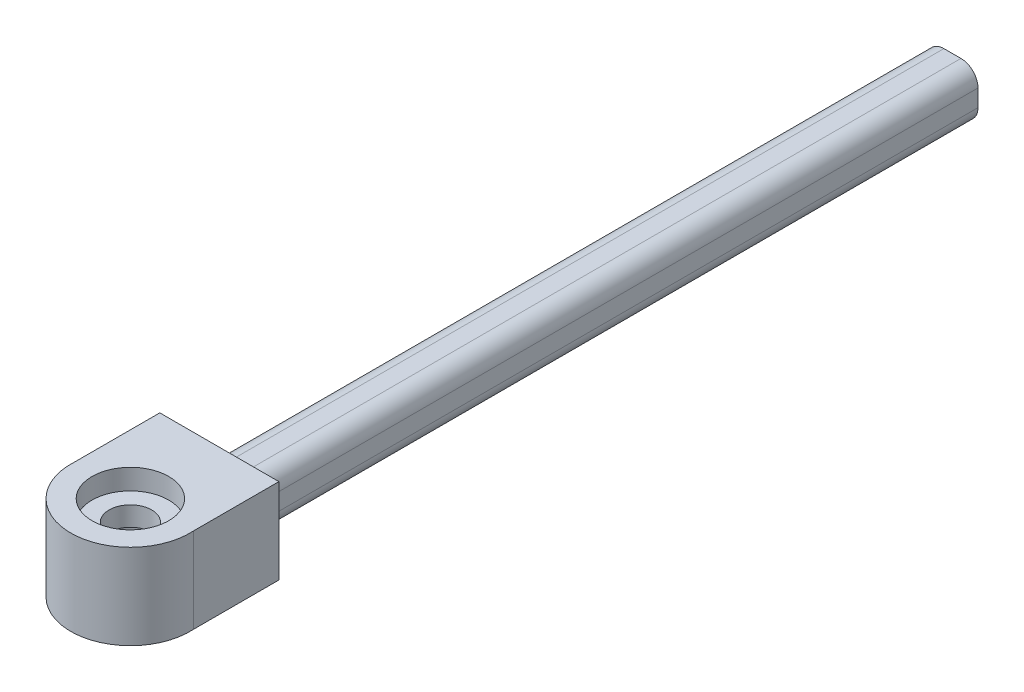
SolidWorks part; units mm, degrees
ref_plane "前视基准面" through (0, 0, 0) normal (0, 0, 1) x (1, 0, 0)
ref_plane "上视基准面" through (0, 0, 0) normal (0, 1, 0) x (1, 0, 0)
ref_plane "右视基准面" through (0, 0, 0) normal (1, 0, 0) x (0, 0, -1)
other "Configuration Table"
sketch "草图1" plane through (0, 0, 0) normal (0, 0, 1) x (1, 0, 0)
  line L0 (0, 0) -> (0, 48.7698) construction
  line L1 (-2.4, 0) -> (-3.5, 0)
  line L2 (-3.5, 0) -> (-3.5, 5)
  line L3 (-3.5, 5) -> (-2.25, 5)
  line L4 (-2.25, 5) -> (-2.25, 3.8)
  line L5 (-2.25, 3.8) -> (-1.25, 3.8)
  line L6 (-1.25, 3.8) -> (-1.25, 2.66)
  line L7 (-1.25, 2.66) -> (-2.4, 2.66)
  line L8 (-2.4, 2.66) -> (-2.4, 0)
  dimension "D1" = 5
  dimension "D2" = 3.5
  dimension "D3" = 2.66
  dimension "D4" = 1.2
  dimension "D5" = 4.5
  dimension "D6" = 4.8
  dimension "D7" = 2.5
revolve "旋转1" add sketch "草图1" angle 360 about L0
ref_plane "基准面1" through (0, 2, 0) normal (0, -1, 0) x (-1, 0, 0)
sketch "草图2" plane through (0, 2, 0) normal (0, -1, 0) x (-1, 0, 0)
  line L3 (-3.4932, 0.2187) -> (-3.4932, 5.2187)
  line L4 (-3.4932, 5.2187) -> (3.4932, 5.2187)
  line L5 (3.4932, 5.2187) -> (3.4932, 0.2187)
  circle A1 centre (0, 0) radius 3.5 construction
  arc A2 (3.4932, 0.2187) -> (-3.4932, 0.2187) centre (0, 0) ccw
  dimension "D1" = 5
extrude "凸台-拉伸1" add sketch "草图2" along normal up to surface (2 mm away) up to face at (0, 0, -2.4)
extrude "凸台-拉伸2" add sketch "草图2<2>" against normal up to surface (3 mm away) up to face at (0, 5, -3.5)
sketch "草图2<2>" plane through (0, 2, 0) normal (0, -1, 0) x (-1, 0, 0) same geometry as "草图2"
sketch "草图4" plane through (0, 0, -5.2187) normal (0, 0, -1) x (-1, 0, 0)
  line L4 (0, 0) -> (0, 2) construction
  line L6 (-3.85, 2) -> (3.85, 2) construction
  line L7 (0, 2) -> (3.49, 2) construction
  line L9 (-1.5, 3.5) -> (1.5, 3.5)
  line L10 (-1.5, 3.5) -> (-1.5, 0.5)
  line L11 (-1.5, 0.5) -> (1.5, 0.5)
  line L12 (1.5, 3.5) -> (1.5, 0.5)
  line L13 (-1.5, 3.5) -> (1.5, 0.5) construction
  line L14 (-1.5, 0.5) -> (1.5, 3.5) construction
  dimension "D1" = 2
  dimension "D2" = 3.49
  dimension "D3" = 3
extrude "凸台-拉伸3" add sketch "草图4" along normal blind 40
sketch "草图6" plane through (0, 0, -45.2188) normal (0, 0, -1) x (-1, 0, 0)
  line L0 (-1.5, 3.5) -> (-1.5, 0.5)
  line L1 (-1.5, 0.5) -> (1.5, 0.5)
  line L2 (1.5, 0.5) -> (1.5, 3.5)
  line L3 (1.5, 3.5) -> (-1.5, 3.5)
extrude "凸台-拉伸4" add sketch "草图6" along normal blind 3
sketch "草图8" plane through (1.5, 0, 0) normal (-1, 0, 0) x (0, 0, 1)
  line L0 (-48.2188, 2) -> (-46.7188, 2) construction
  line L1 (-48.2188, 0.5) -> (-48.2188, 3.5) construction
  circle A0 centre (-46.7188, 2) radius 1
  dimension "D2" = 2
  dimension "D1" = 1.5
fillet "圆角1" radius 1 4 edges at (1.5, 0.5, -26.7188) (-1.5, 0.5, -26.7188) (-1.5, 3.5, -26.7188) (1.5, 3.5, -26.7188)
